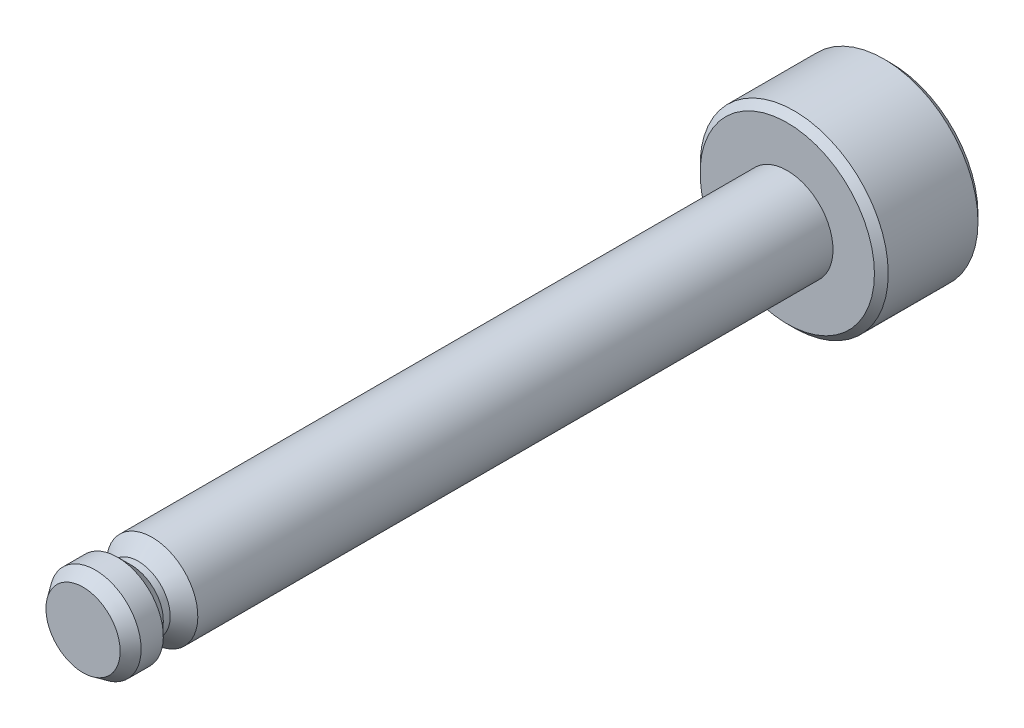
SolidWorks part; units mm, degrees
ref_plane "Front" through (0, 0, 0) normal (0, 0, 1) x (1, 0, 0)
ref_plane "Top" through (0, 0, 0) normal (0, 1, 0) x (1, 0, 0)
ref_plane "Right" through (0, 0, 0) normal (1, 0, 0) x (0, 0, -1)
sketch "Sketch2" plane through (0, 0, 0) normal (0, 0, 1) x (1, 0, 0)
  circle A0 centre (0, 0) radius 1.325
  dimension "D1" = 2.65
extrude "Shaft" add sketch "Sketch2" along normal blind 20.4
sketch "Sketch5" plane through (0, 0, 0) normal (0, 0, 1) x (1, 0, 0)
  circle A0 centre (0, 0) radius 2.725
  dimension "D1" = 5.45
extrude "Head" add sketch "Sketch5" against normal blind 3
chamfer "Chamfer1" distance 0.25 angle 55 1 edges at (1.325, 0, 20.4) first distance on face at (1.325, 0, 20.4)
chamfer "Deburs" distance 0.2 angle 45 2 edges at (2.725, 0, 0) (2.725, 0, -3)
sketch "Sketch6" plane through (0, 0, 0) normal (1, 0, 0) x (0, 0, -1)
  line L0 (0, 0) -> (-18.9, 0) construction
  line L1 (-18.9, 0) -> (-18.9, 0.925) construction
  line L2 (0, 1.325) -> (-20.043, 1.325) construction
  line L3 (-19.4, 1.325) -> (-18.4, 1.325)
  line L4 (-18.4, 1.325) -> (-18.8, 0.925)
  line L5 (-18.8, 0.925) -> (-19, 0.925)
  line L6 (-19, 0.925) -> (-19.4, 1.325)
  line L7 (-18.9, 0.925) -> (-18.9, 1.325) construction
  dimension "D1" = 18.9
  dimension "D2" = 0.4
  dimension "D3" = 1
revolve "e-Clip Notch Long" cut sketch "Sketch6" angle 360 about L0
equation "\"D1@Sketch2\"=\"Plastic Hardware OD@Box Assy.Assembly\""
equation "\"D1\"= \"Countersink Diameter@Box Assy.Assembly\" - .3mm"
equation "\"D1@Head\"=\"Countersink Depth@Box Assy.Assembly\""
equation "\"Length\"= 20mm"
equation "\"D1@Shaft\"=\"Length\"+.4mm"
equation "\"D1@Sketch6\"=\"Length\"-1.1mm"
